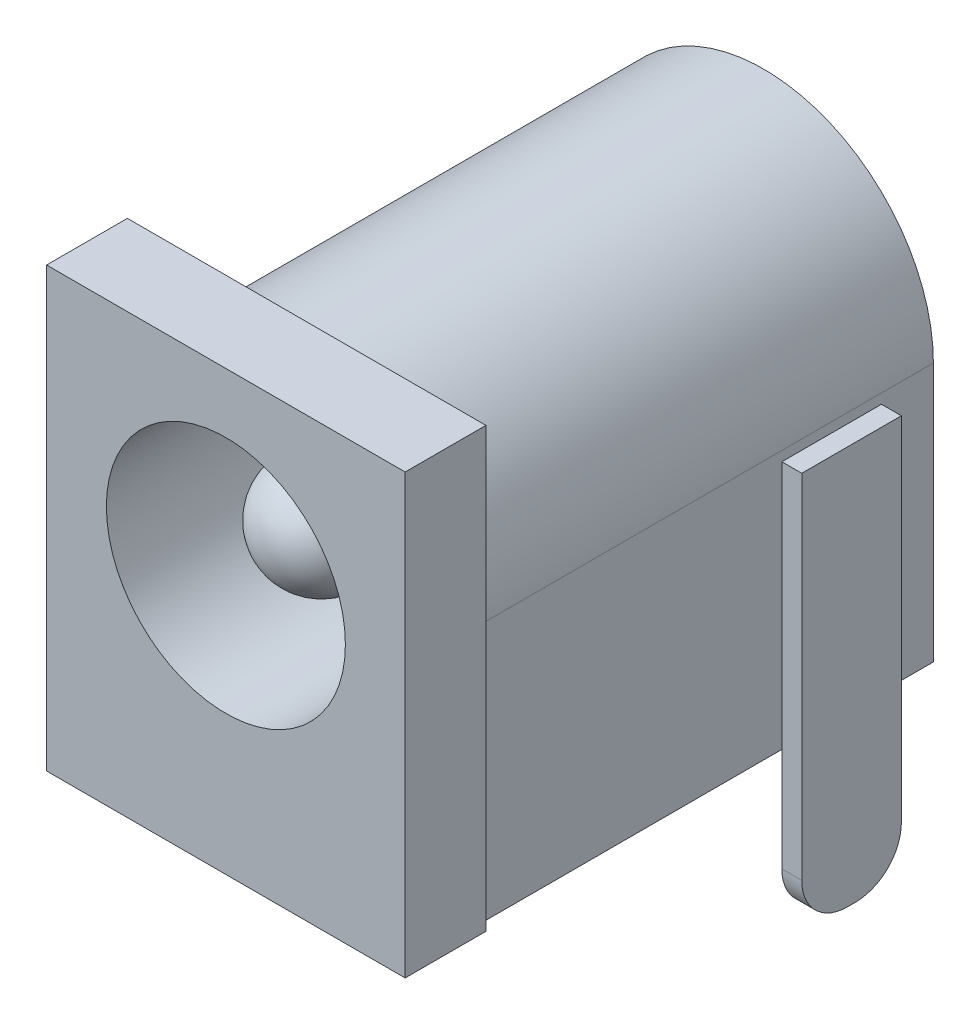
SolidWorks part; units mm, degrees
ref_plane "Front Plane" through (0, 0, 0) normal (0, 0, 1) x (1, 0, 0)
ref_plane "Top Plane" through (0, 0, 0) normal (0, 1, 0) x (1, 0, 0)
ref_plane "Right Plane" through (0, 0, 0) normal (1, 0, 0) x (0, 0, -1)
sketch "Sketch1" plane through (0, 0, 0) normal (0, 0, 1) x (1, 0, 0)
  line L1 (0, 0) -> (9, 0)
  line L2 (0, 0) -> (0, 11)
  line L3 (0, 11) -> (9, 11)
  line L4 (9, 0) -> (9, 11)
  dimension "D1" = 9
  dimension "D2" = 11
extrude "Extrude1" add sketch "Sketch1" along normal blind 13.5
sketch "Sketch2" plane through (0, 0, 0) normal (0, 0, -1) x (-1, 0, 0)
  line L0 (-4.5, 11) -> (-4.5, -0.5502) construction
  line L1 (-9, 11) -> (0, 11) construction
  line L2 (-9.6061, 6.5) -> (2.3319, 6.5) construction
  line L3 (0, 0) -> (-9, 0) construction
  line L4 (-8.7599, 6.5) -> (-8.7599, 0)
  line L5 (-10.2355, 11.2863) -> (1.2761, 11.2863)
  line L6 (-10.2355, 11.2863) -> (-10.2355, 0)
  line L7 (-10.2355, 0) -> (-8.7599, 0)
  line L8 (1.2761, 11.2863) -> (1.2761, 0)
  line L9 (-0.2401, 6.5) -> (-0.2401, 0)
  line L10 (1.2761, 0) -> (-0.2401, 0)
  line L11 (-0.2401, 0) -> (-0.1451, 0.0995)
  arc A0 (-0.2401, 6.5) -> (-8.7599, 6.5) centre (-4.5, 6.5) ccw
  dimension "D1" = 6.5
extrude "Cut-Extrude1" cut sketch "Sketch2" against normal blind 11.4722
sketch "Sketch3" plane through (0, 0, 0) normal (0, -1, 0) x (1, 0, 0)
  line L0 (4.5, 13.5) -> (4.5, -0.4029) construction
  line L1 (0, 13.5) -> (9, 13.5) construction
  line L2 (7.4651, 5.8) -> (2.4013, 5.8) construction
  line L3 (5.9633, 2.8) -> (9.4483, 2.8) construction
  line L4 (6.8105, -0.2) -> (1.8429, -0.2) construction
  line L5 (9.4, 3.9293) -> (9.4, 1.5033) construction
  line L7 (5.75, 6.05) -> (3.25, 6.05)
  line L8 (5.75, 6.05) -> (5.75, 5.55)
  line L9 (5.75, 5.55) -> (3.25, 5.55)
  line L10 (3.25, 6.05) -> (3.25, 5.55)
  line L11 (9.5054, 4.05) -> (9.0054, 4.05)
  line L12 (9.5054, 4.05) -> (9.5054, 1.55)
  line L13 (9.5054, 1.55) -> (9.0054, 1.55)
  line L14 (9.0054, 4.05) -> (9.0054, 1.55)
  line L15 (5.75, -0.3264) -> (3.25, -0.3264)
  line L16 (5.75, -0.3264) -> (5.75, 0.1736)
  line L17 (5.75, 0.1736) -> (3.25, 0.1736)
  line L18 (3.25, -0.3264) -> (3.25, 0.1736)
  dimension "D1" = 7.7
  dimension "D2" = 3
  dimension "D3" = 6
  dimension "D4" = 4.9
  dimension "D5" = 0.5
  dimension "D6" = 0.25
  dimension "D7" = 2.5
  dimension "D8" = 1.25
  dimension "D9" = 1.25
  dimension "D10" = 1.25
extrude "Extrude2" add sketch "Sketch3" along normal blind 3.5 and the other way blind 6.5
sketch "Sketch4" plane through (9.5054, 0, 0) normal (1, 0, 0) x (0, 0, -1)
  line L0 (-1.55, 0.4012) -> (-0.3179, 0.4012)
  line L3 (-5.0956, -4.0453) -> (-0.3179, -4.0453)
  line L4 (-5.0956, -4.0453) -> (-5.0956, 0.4012)
  line L5 (-5.0956, 0.4012) -> (-4.05, 0.4012)
  line L8 (-4.05, 6.5) -> (-4.05, -3.5)
  line L9 (-4.05, -3.5) -> (-1.55, -3.5)
  line L10 (-1.55, -3.5) -> (-1.55, 6.5)
  line L11 (-0.3179, -4.0453) -> (-0.3179, 0.4012)
  line L12 (-1.55, 6.5) -> (-4.05, 6.5)
  line L13 (-4.05, 0.4012) -> (-4.05, -2.35)
  line L14 (-2.9, -3.5) -> (-2.7, -3.5)
  line L15 (-1.55, -2.35) -> (-1.55, 0.4012)
  arc A0 (-4.05, -2.35) -> (-2.9, -3.5) centre (-2.9, -2.35) ccw
  arc A1 (-2.7, -3.5) -> (-1.55, -2.35) centre (-2.7, -2.35) ccw
  dimension "D2" = 1.15
  dimension "D1" = 0
extrude "Cut-Extrude2" cut sketch "Sketch4" against normal up to next (0.5 mm away)
sketch "Sketch5" plane through (0, 0, -0.3264) normal (0, 0, -1) x (-1, 0, 0)
  line L0 (-3.25, -0.5583) -> (-2.2475, -0.5583)
  line L1 (-6.9661, -0.5583) -> (-5.75, -0.5583)
  line L2 (-6.9661, -0.5583) -> (-6.9661, -4.0517)
  line L3 (-6.9661, -4.0517) -> (-2.2475, -4.0517)
  line L4 (-5.75, 6.5) -> (-5.75, -3.5)
  line L5 (-5.75, -3.5) -> (-3.25, -3.5)
  line L6 (-3.25, -3.5) -> (-3.25, 6.5)
  line L7 (-3.25, 6.5) -> (-5.75, 6.5)
  line L8 (-5.75, -0.5583) -> (-5.75, -2.35)
  line L9 (-4.6, -3.5) -> (-4.4, -3.5)
  line L10 (-3.25, -2.35) -> (-3.25, -0.5583)
  line L11 (-2.2475, -0.5583) -> (-2.2475, -4.0517)
  arc A0 (-5.75, -2.35) -> (-4.6, -3.5) centre (-4.6, -2.35) ccw
  arc A1 (-4.4, -3.5) -> (-3.25, -2.35) centre (-4.4, -2.35) ccw
  dimension "D2" = 1.15
  dimension "D1" = 0
extrude "Cut-Extrude3" cut sketch "Sketch5" against normal up to surface (6.3764 mm away) up to face at (4.5, -1.75, 6.05)
sketch "Sketch6" plane through (0, 0, 13.5) normal (0, 0, 1) x (1, 0, 0)
  line L0 (4.5, 11) -> (4.5, 2.064) construction
  line L1 (9, 11) -> (0, 11) construction
  line L2 (-1.7548, 6.5) -> (13.0449, 6.5) construction
  line L3 (0, 0) -> (9, 0) construction
  circle A0 centre (4.5, 6.5) radius 3
  dimension "D1" = 6
  dimension "D2" = 6.5
extrude "Cut-Extrude4" cut sketch "Sketch6" against normal blind 10.5
sketch "Sketch7" plane through (0, 0, 3) normal (0, 0, 1) x (1, 0, 0)
  circle A0 centre (4.5, 6.5) radius 1.3412
  circle A1 centre (4.5, 6.5) radius 3
  circle A2 centre (4.5, 6.5) radius 3 construction
  dimension "D1" = 0
extrude "Extrude3" add sketch "Sketch7" along normal blind 8.5
dome "Dome1" faces to dome 1 distance 1 reverse direction no elliptical dome no face at (5.8412, 6.5, 11.5) parameters "D1"=1
equation "\"D6@Sketch3\" = \"D5@Sketch3\"/2"
equation "\"D8@Sketch3\" = \"D7@Sketch3\"/2"
equation "\"D9@Sketch3\" = \"D8@Sketch3\""
equation "\"D10@Sketch3\" = \"D8@Sketch3\""
